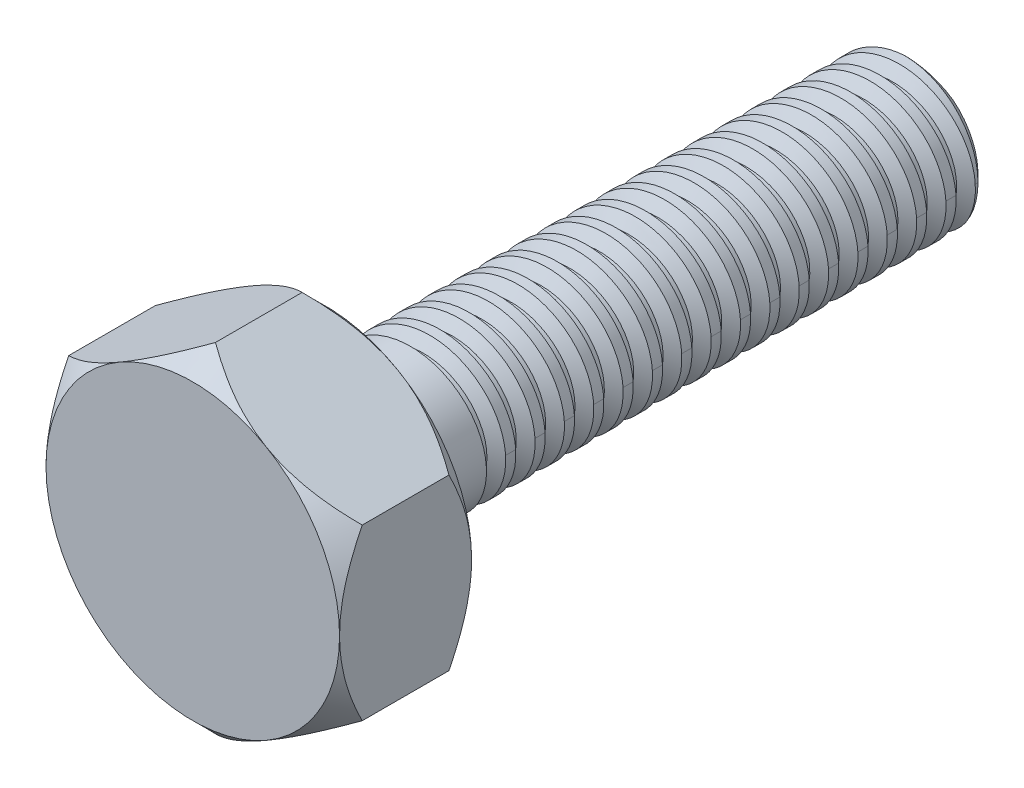
SolidWorks part; units mm, degrees
ref_plane "Front Plane" through (0, 0, 0) normal (0, 0, 1) x (1, 0, 0)
ref_plane "Top Plane" through (0, 0, 0) normal (0, 1, 0) x (1, 0, 0)
ref_plane "Right Plane" through (0, 0, 0) normal (1, 0, 0) x (0, 0, -1)
sketch "Sketch1" plane through (0, 0, 0) normal (0, 0, 1) x (1, 0, 0)
  line L1 (0, 11.547) -> (-10, 5.7735)
  line L2 (-10, 5.7735) -> (-10, -5.7735)
  line L3 (-10, -5.7735) -> (0, -11.547)
  line L4 (0, -11.547) -> (10, -5.7735)
  line L5 (10, -5.7735) -> (10, 5.7735)
  line L6 (10, 5.7735) -> (0, 11.547)
  circle A0 centre (0, 0) radius 10 construction
  dimension "D1" = 20
extrude "Boss-Extrude1" add sketch "Sketch1" along normal mid plane 9
sketch "Sketch2" plane through (0, 0, 4.5) normal (0, 0, 1) x (1, 0, 0)
  line L0 (0, 11.547) -> (-10, 5.7735) construction
  circle A0 centre (0, 0) radius 10
extrude "Cut-Extrude1" cut sketch "Sketch2" against normal blind 9 draft 45 flip side to cut
mirror "Mirror1" about plane through (0, 0, 0) normal (0, 0, 1) of "Cut-Extrude1"
sketch "Sketch3" plane through (0, 0, -4.5) normal (0, 0, -1) x (-1, 0, 0)
  circle A0 centre (0, 0) radius 5
  dimension "D1" = 10
extrude "Boss-Extrude2" add sketch "Sketch3" along normal blind 40
chamfer "Chamfer1" distance 0.5 angle 45 1 edges at (-5, 0, -44.5)
thread "Thread1" pitch 1.5 method cut profile "Thread Profile9" start angle 0, offset 5, length 0, pitch 2, diameter 10
ref_plane "Plane9" through (-5, 0, -9.5) normal (0, -1, 0) x (-1, 0, 0)
sketch "Thread Profile9" plane through (-5, 0, -9.5) normal (0, -1, 0) x (-1, 0, 0)
  line L0 (0, 0) -> (0, 1.5) construction
  line L11 (0, 0) -> (0, 1.3125)
  line L12 (0, 1.3125) -> (-0.8119, 0.8437)
  line L13 (-0.8119, 0.8437) -> (-0.8119, 0.4687)
  line L15 (-0.8119, 0.4687) -> (0, 0)
  line L17 (-0.8119, 0.6562) -> (0, 0.6562) construction
  point P2 (0, 0)
  dimension "Pitch" = 1.5
  dimension "Profile_Angle" = 60
  dimension "Profile_Land" = 0.375
  dimension "Profile_Height" = 0.8119
sketch "Sketch30" plane through (0, 0, 0) normal (0, 1, 0) x (1, 0, 0)
  line L4 (-5, 9.5) -> (-4.1881, 9.9687)
  line L5 (-4.1881, 9.9687) -> (-4.1881, 10.3437)
  line L6 (-4.1881, 10.3437) -> (-5, 10.8125)
  line L7 (-5, 10.8125) -> (-5, 9.5)
  line L8 (-5, 9.5) -> (-4.1881, 9.9687)
  line L9 (-4.1881, 9.9687) -> (-4.1881, 10.3437)
  line L10 (-4.1881, 10.3437) -> (-5, 10.8125)
  line L11 (-5, 10.8125) -> (-5, 9.5)
  dimension "D1" = 0
extrude "Cut-Extrude2" cut sketch "Sketch30" against normal through all and the other way through all
